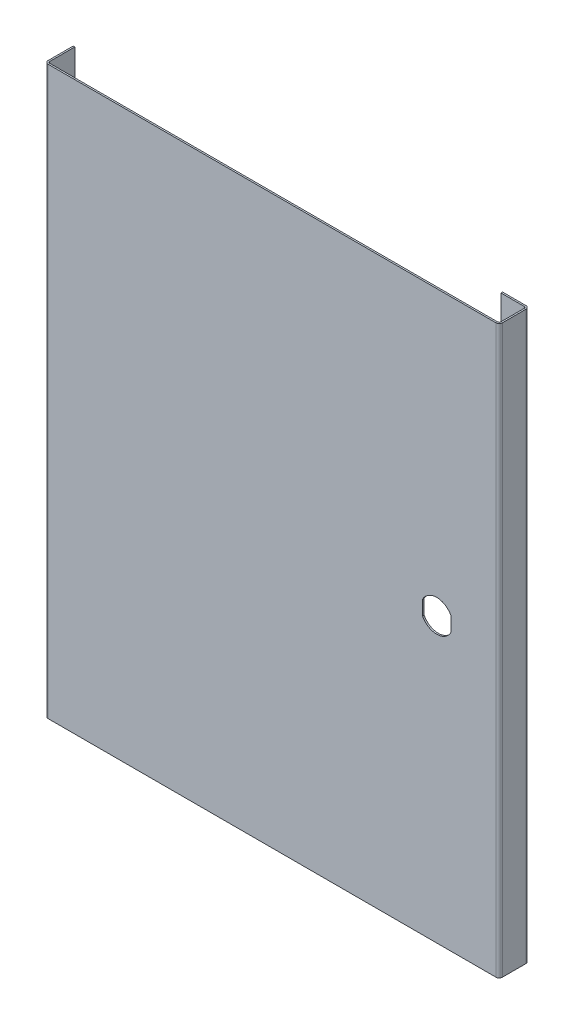
SolidWorks part; units mm, degrees
note: The reader was unsure of these and kept them because the rebuilt part matched: thickness of "Base-Flange1", "Edge-Flange1", "Edge-Flange2", "Sheet-Metal1", "Sheet-Metal2", "Sheet-Metal3", "Sheet-Metal5"; flange length of "Edge-Flange1", "Edge-Flange2".
ref_plane "Front Plane" through (0, 0, 0) normal (0, 0, 1) x (1, 0, 0)
ref_plane "Top Plane" through (0, 0, 0) normal (0, 1, 0) x (1, 0, 0)
ref_plane "Right Plane" through (0, 0, 0) normal (1, 0, 0) x (0, 0, -1)
sketch "Sketch1" plane through (0, 0, 0) normal (0, 0, 1) x (1, 0, 0)
  line L1 (-128.25, -160) -> (128.25, -160)
  line L2 (-128.25, -160) -> (-128.25, 160)
  line L3 (-128.25, 160) -> (128.25, 160)
  line L4 (128.25, -160) -> (128.25, 160)
  line L5 (-128.25, -160) -> (128.25, 160) construction
  line L6 (-128.25, 160) -> (128.25, -160) construction
  point P0 (0, 0)
  dimension "D1" = 256.5
  dimension "D2" = 320
base flange "Base-Flange1" sketch "Sketch1" thickness 0.9 reverse thickness direction no parameters "D1"=0.9
edge flange "Edge-Flange1" sketch "Sketch10" flange profiles "Sketch10", "Sketch11" flange angle 90 flange length 16 flange position material inside bend radius 0.9 thickness 0.9 relief rectangular parameters "D1"=3, "D6"=10, "D8"=1
sketch "Sketch10" plane through (128.25, 0, -0.9) normal (1, 0, 0) x (0, -1, 0)
  line L0 (160, 0) -> (-160, 0) construction
  line L1 (160, 0) -> (-160, 0)
  line L2 (-160, 0) -> (-160, 15.1)
  line L3 (-160, 15.1) -> (160, 15.1)
  line L4 (160, 15.1) -> (160, 0)
sketch "Sketch11" plane through (-128.25, 0, -0.9) normal (-1, 0, 0) x (0, 1, 0)
  line L0 (160, 0) -> (-160, 0) construction
  line L1 (160, 0) -> (-160, 0)
  line L2 (-160, 0) -> (-160, 15.1)
  line L3 (-160, 15.1) -> (160, 15.1)
  line L4 (160, 15.1) -> (160, 0)
bend "EdgeBend1" bend radius 0.9 bend angle 90 parameters "D5"=1
bend "EdgeBend2" bend radius 0.9 bend angle 90 parameters "D5"=2
edge flange "Edge-Flange2" sketch "Sketch17" flange angle 90 flange length 15 flange position material outside bend radius 0.9 thickness 0.9 relief rectangular parameters "D1"=3, "D6"=10, "D8"=1
sketch "Sketch17" plane through (127.35, 0, -16) normal (0, 0, -1) x (0, -1, 0)
  line L0 (160, 0) -> (-160, 0) construction
  line L1 (160, 0) -> (-160, 0)
  line L2 (-160, 0) -> (-160, 14.1)
  line L3 (-160, 14.1) -> (160, 14.1)
  line L4 (160, 14.1) -> (160, 0)
bend "EdgeBend4" bend radius 0.9 bend angle 90 parameters "D5"=4
sketch "Sketch24" plane through (0, 0, 0) normal (0, 0, 1) x (1, 0, 0)
  line L0 (101, 4.1231) -> (101, -4.1231)
  line L1 (85, 4.1231) -> (85, -4.1231)
  arc A0 (85, -4.1231) -> (101, -4.1231) centre (93, 0) ccw
  arc A1 (101, 4.1231) -> (85, 4.1231) centre (93, 0) ccw
  dimension "D1" = 9
  dimension "D2" = 93
  dimension "D3" = 16
  dimension "D4" = 8
extrude "Cut-Extrude1" cut sketch "Sketch24" against normal through all normal cut yes
sketch "Bend-Lines1" [suppressed] plane through (0, 0, 0) normal (0, 1, 0) x (1, 0, 0)
sketch "Bounding-Box1" [suppressed] plane through (0, 0, 0) normal (0, 1, 0) x (1, 0, 0)
sheet metal parameters "Sheet-Metal1" thickness 0.9 parameters "D1"=3, "D7"=1.2
flat pattern "Flat-Pattern1" [suppressed]
sketch "Bend-Lines2" plane through (0, 0, 0) normal (0, 1, 0) x (1, 0, 0)
sketch3d "Bounding-Box2" [suppressed]
  line L0 (-130, 210, 0) -> (-130, -210, 0) construction
  line L1 (130, 210, 0) -> (130, -210, 0) construction
  line L2 (-130, 210, 0) -> (130, 210, 0) construction
  line L3 (-130, -210, 0) -> (130, -210, 0) construction
sheet metal parameters "Sheet-Metal2" thickness 0.9 parameters "D1"=3, "D7"=1.2
flat pattern "Flat-Pattern1"
sketch "Bend-Lines2" plane through (0, 0, 0) normal (0, 0, 1) x (1, 0, 0)
  line L0 (-129.6389, 210) -> (-129.6389, -210) construction
  line L1 (129.6389, -210) -> (129.6389, 210) construction
  line L2 (-129.6389, 210) -> (-129.6389, -210) construction
  line L3 (129.6389, -210) -> (129.6389, 210) construction
sketch3d "Bounding-Box2" [suppressed]
  line L0 (143.0779, 210, 0) -> (143.0779, -210, 0) construction
  line L1 (-143.0779, 210, 0) -> (-143.0779, -210, 0) construction
  line L2 (143.0779, 210, 0) -> (-143.0779, 210, 0) construction
  line L3 (143.0779, -210, 0) -> (-143.0779, -210, 0) construction
bend of the flat pattern "Flatten-<EdgeBend1>1"
bend of the flat pattern "Flatten-<EdgeBend2>1"
sheet metal parameters "Sheet-Metal3" thickness 0.9 parameters "D1"=3, "D7"=1.2
flat pattern "Flat-Pattern1"
sketch "Bend-Lines2" plane through (0, 0, 0) normal (0, 0, 1) x (1, 0, 0)
  line L0 (-129.6389, 210) -> (-129.6389, -210) construction
  line L1 (129.6389, -210) -> (129.6389, 210) construction
  line L2 (-129.6389, 210) -> (-129.6389, -210) construction
  line L3 (129.6389, -210) -> (129.6389, 210) construction
  line L4 (147.7168, -210) -> (147.7168, 210) construction
  line L5 (-147.7168, 210) -> (-147.7168, -210) construction
  line L6 (147.7168, -210) -> (147.7168, 210) construction
  line L7 (-147.7168, 210) -> (-147.7168, -210) construction
sketch3d "Bounding-Box2" [suppressed]
  line L0 (166.1558, 210, 0) -> (166.1558, -210, 0) construction
  line L1 (-166.1558, 210, 0) -> (-166.1558, -210, 0) construction
  line L2 (166.1558, 210, 0) -> (-166.1558, 210, 0) construction
  line L3 (166.1558, -210, 0) -> (-166.1558, -210, 0) construction
bend of the flat pattern "Flatten-<EdgeBend1>1"
bend of the flat pattern "Flatten-<EdgeBend2>1"
bend of the flat pattern "Flatten-<EdgeBend4>1"
sheet metal parameters "Sheet-Metal5" thickness 0.9 parameters "D1"=3, "D7"=1.2
flat pattern "Flat-Pattern1"
sketch "Bend-Lines2" plane through (0, 0, 0) normal (0, 0, 1) x (1, 0, 0)
  line L0 (-127.3689, 160) -> (-127.3689, -160) construction
  line L1 (127.3689, -160) -> (127.3689, 160) construction
  line L2 (-127.3689, 160) -> (-127.3689, -160) construction
  line L3 (127.3689, -160) -> (127.3689, 160) construction
  line L4 (142.5067, -160) -> (142.5067, 160) construction
  line L6 (142.5067, -160) -> (142.5067, 160) construction
sketch3d "Bounding-Box2" [suppressed]
  line L0 (156.6257, 160, 0) -> (156.6257, -160, 0) construction
  line L1 (-142.4878, 160, 0) -> (-142.4878, -160, 0) construction
  line L2 (156.6257, 160, 0) -> (-142.4878, 160, 0) construction
  line L3 (156.6257, -160, 0) -> (-142.4878, -160, 0) construction
bend of the flat pattern "Flatten-<EdgeBend1>1"
bend of the flat pattern "Flatten-<EdgeBend2>1"
bend of the flat pattern "Flatten-<EdgeBend4>1"
